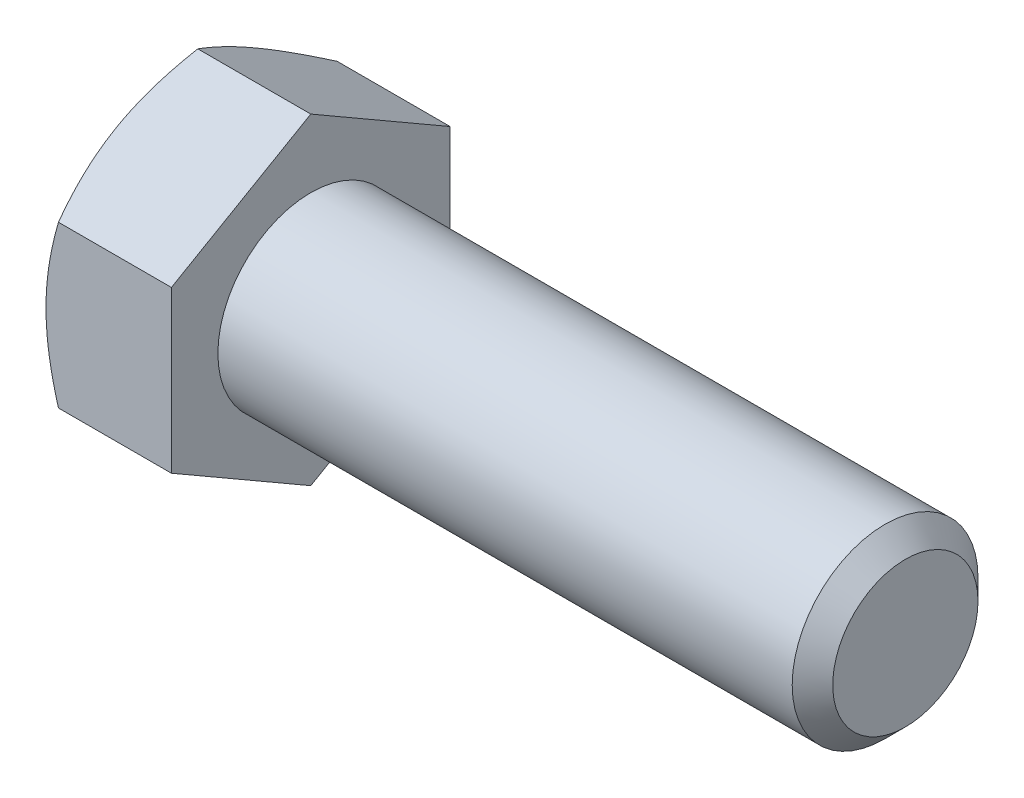
SolidWorks part; units mm, degrees
ref_plane "Front Plane" through (0, 0, 0) normal (0, 0, 1) x (1, 0, 0)
ref_plane "Top Plane" through (0, 0, 0) normal (0, 1, 0) x (1, 0, 0)
ref_plane "Right Plane" through (0, 0, 0) normal (1, 0, 0) x (0, 0, -1)
sketch "Sketch1" plane through (0, 0, 0) normal (0, 0, 1) x (1, 0, 0)
  line L0 (-30.7578, 0) -> (30.7578, 0) construction
  line L1 (30.7578, 7.9375) -> (30.7578, -7.9375) construction
  line L2 (-20.0422, 11.9062) -> (-20.0422, -11.9062) construction
  line L3 (-30.7578, 11.9062) -> (-30.7578, -11.9062) construction
  point P9 (-20.0422, 0)
  point P10 (22.676, -7.9375)
  dimension "Screw Dia" = 15.875
  dimension "Hex" = 23.8125
  dimension "Head Ht" = 10.7156
  dimension "Screw Lenght" = 50.8
  dimension "D1" = 8.0818
ref_plane "Plane2" through (30.7578, 0, 0) normal (1, 0, 0) x (0, 0, -1)
sketch "Sketch5" plane through (30.7578, 0, 0) normal (1, 0, 0) x (0, 0, -1)
  circle A0 centre (0, 0) radius 7.9375
extrude "Boss-Extrude3" add sketch "Sketch5" against normal up to vertex (50.8 mm away) up to point (-20.0422, 0, 0)
sketch "Sketch9" plane through (30.7578, 0, 0) normal (1, 0, 0) x (0, 0, -1)
  circle A1 centre (0, 0) radius 7.9375
  circle A2 centre (0, 0) radius 7.9375
  dimension "D1" = 0
curve "Helix/Spiral1" pitch 2.3091 height 53.1091 turns 23 parameters "Pitch"=2.3091
chamfer "Chamfer1" distance 1.7318 angle 45 1 edges at (30.7578, 0, -7.9375)
sketch "Sketch10" plane through (0, 0, 0) normal (0, 0, 1) x (1, 0, 0)
  line L0 (30.7578, 7.9375) -> (31.6237, 6.4377)
  line L1 (31.6237, 6.4377) -> (31.9124, 6.4377)
  line L2 (31.9124, 6.4377) -> (32.7783, 7.9375)
  line L3 (30.7578, 7.9375) -> (32.7783, 7.9375)
  line L4 (31.768, 7.9375) -> (31.768, 6.4377) construction
  line L5 (31.1908, 7.1876) -> (32.3453, 7.1876) construction
  dimension "D1" = 60
  dimension "D2" = 0.2886
  dimension "D3" = 1.1545
sweep "Cut-Sweep1" [suppressed] cut profiles "Sketch10" path "Helix/Spiral1"
sketch "Sketch6" plane through (-20.0422, 0, 0) normal (-1, 0, 0) x (0, 0, 1)
  line L0 (0, 11.9062) -> (0, -11.9062) construction
  line L1 (11.9062, 6.8741) -> (0, 13.7482)
  line L2 (0, 13.7482) -> (-11.9062, 6.8741)
  line L3 (-11.9062, 6.8741) -> (-11.9062, -6.8741)
  line L4 (-11.9062, -6.8741) -> (0, -13.7482)
  line L5 (0, -13.7482) -> (11.9063, -6.8741)
  line L6 (11.9063, -6.8741) -> (11.9062, 6.8741)
  circle A0 centre (0, 0) radius 11.9062 construction
extrude "Boss-Extrude4" add sketch "Sketch6" along normal up to vertex (10.7156 mm away) up to point (-30.7578, -11.9062, 0)
sketch "Sketch7" plane through (-30.7578, 0, 0) normal (-1, 0, 0) x (0, 0, 1)
  circle A0 centre (0, 0) radius 11.9062 construction
  circle A1 centre (0, 0) radius 11.9062
sketch "Sketch8" plane through (-30.7578, 0, 0) normal (-1, 0, 0) x (0, 0, 1)
  circle A0 centre (0, 0) radius 11.9062 construction
  circle A1 centre (0, 0) radius 11.9062
extrude "Cut-Extrude3" cut sketch "Sketch8" against normal through all draft 60 flip side to cut
sketch "Sketch12" plane through (-30.7578, 0, 0) normal (-1, 0, 0) x (0, 0, 1)
  line L0 (0, 9.1678) -> (0, 5.1197) construction
  line L1 (0.3572, 9.1678) -> (0.3572, 5.1197)
  line L2 (-0.3572, 9.1678) -> (-0.3572, 5.1197)
  line L3 (0, 7.9375) -> (0, -7.9375) construction
  arc A0 (0.3572, 9.1678) -> (-0.3572, 9.1678) centre (0, 9.1678) ccw
  arc A1 (-0.3572, 5.1197) -> (0.3572, 5.1197) centre (0, 5.1197) ccw
  circle A3 centre (0, 0) radius 4.7625 construction
  circle A4 centre (0, 0) radius 9.525 construction
  point P2 (0, 7.1438)
  dimension "D1" = 9.525
  dimension "D3" = 19.05
  dimension "D2" = 0.7144
extrude "Cut-Extrude4" cut sketch "Sketch12" against normal blind 0.254
pattern_circular "CirPattern1" count 6 over 360 about axis through (-20.0422, 0, 0) along (1, 0, 0) of "Cut-Extrude4"
equation "\"D2@Sketch10\" = \"Pitch@Helix/Spiral1\"*.125"
equation "\"D3@Sketch10\" = \"Pitch@Helix/Spiral1\"*.5"
equation "\"D3@Helix/Spiral1\" = \"Screw Lenght@Sketch1\"+\"Pitch@Helix/Spiral1\""
equation "\"D1@Chamfer1\" = \"Pitch@Helix/Spiral1\"*.75"
equation "\"D1@Sketch12\" = \"Hex@Sketch1\"*.4"
equation "\"D3@Sketch12\" = \"Hex@Sketch1\"*.8"
equation "\"D2@Sketch12\" = \"Hex@Sketch1\"*.03"
equation "\"D1@Sketch1\" = \"Pitch@Helix/Spiral1\"*3.5"
